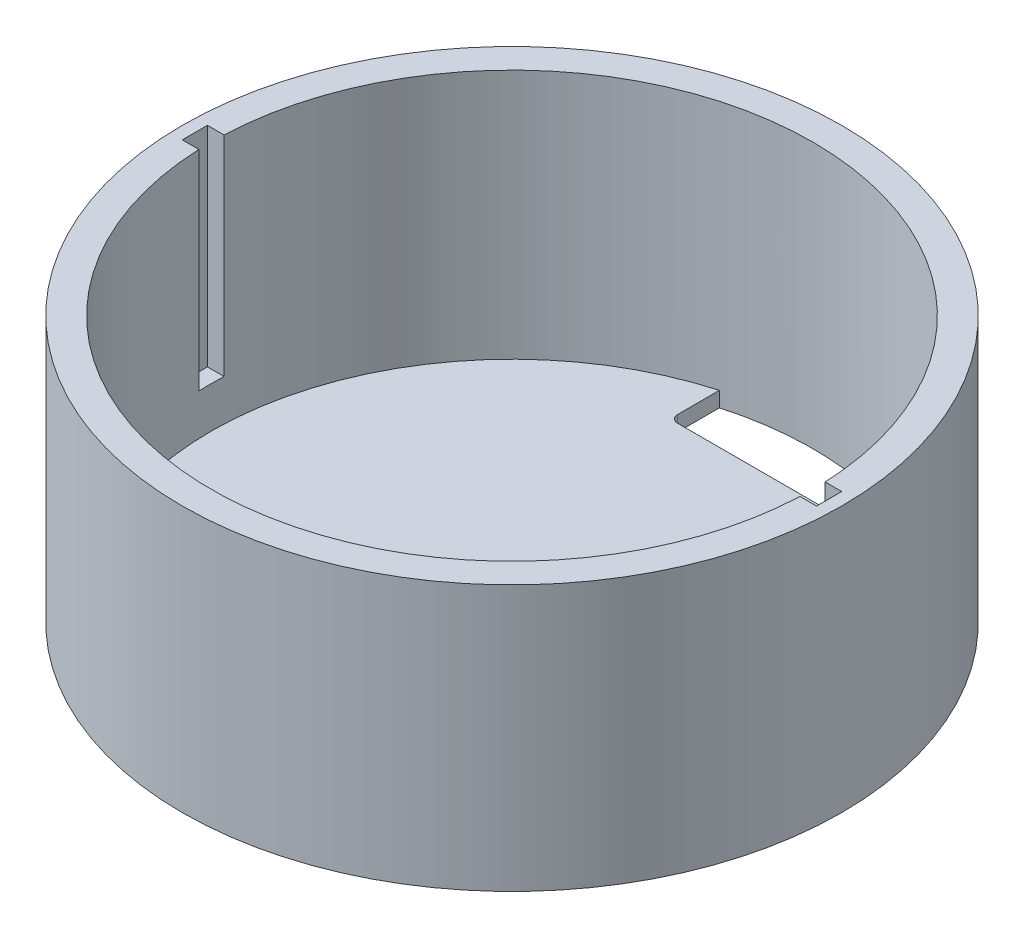
SolidWorks part; units mm, degrees
ref_plane "Front Plane" through (0, 0, 0) normal (0, 0, 1) x (1, 0, 0)
ref_plane "Top Plane" through (0, 0, 0) normal (0, 1, 0) x (1, 0, 0)
ref_plane "Right Plane" through (0, 0, 0) normal (1, 0, 0) x (0, 0, -1)
sketch "Sketch1" plane through (0, 0, 0) normal (0, 1, 0) x (1, 0, 0)
  line L8 (11.6924, 37.8836) -> (11.6924, 32.3302)
  line L9 (-10.8076, 32.6359) -> (-10.8076, 38.1454)
  line L12 (-9.8076, 31.6359) -> (10.6924, 31.6359)
  line L13 (11.6924, 37.8836) -> (11.6924, 32.6359)
  line L14 (-41.8009, 1.6592) -> (41.8009, 1.6592)
  line L15 (-41.8009, 1.6592) -> (-41.8009, -1.6592)
  line L16 (-41.8009, -1.6592) -> (41.8009, -1.6592)
  line L17 (41.8009, 1.6592) -> (41.8009, -1.6592)
  line L18 (-41.8009, 1.6592) -> (41.8009, -1.6592) construction
  line L19 (-41.8009, -1.6592) -> (41.8009, 1.6592) construction
  arc A5 (-10.8076, 32.6359) -> (-9.8076, 31.6359) centre (-9.8076, 32.6359) ccw
  arc A6 (10.6924, 31.6359) -> (11.6924, 32.6359) centre (10.6924, 32.6359) ccw
  circle A7 centre (0, 0) radius 4.75
  circle A10 centre (0, 0) radius 39.6469
  circle A11 centre (0, 0) radius 43.4563
  dimension "D1" = 1
  dimension "D2" = 1
  dimension "D3" = 86.9126
extrude "Boss-Extrude10" add sketch "Sketch1" along normal blind 35 contours A11 A10 L14 L17 L16 L15 region at (-42.2272, 0, 0)
extrude "Boss-Extrude18" add sketch "Sketch1<17>" along normal blind 7.4216 contours A10 L16 L17 L14 | A10 L14 L15 L16 region at (40.7181, 0, 0) region at (-40.7181, 0, 0)
sketch "Sketch1<17>" plane through (0, 0, 0) normal (0, 1, 0) x (1, 0, 0) same geometry as "Sketch1"
extrude "Boss-Extrude19" add sketch "Sketch1<18>" along normal blind 2 contours L14 A10 L8 A6 L12 A5 A7 | L16 A10 L14 A7 | L14 A10 L16 A7 | L16 A10 A7 region at (-0.0294, 0, -16.4866) region at (22.1433, 0, 0) region at (-22.1433, 0, 0) region at (0, 0, 17.8544)
sketch "Sketch1<18>" plane through (0, 0, 0) normal (0, 1, 0) x (1, 0, 0) same geometry as "Sketch1"
